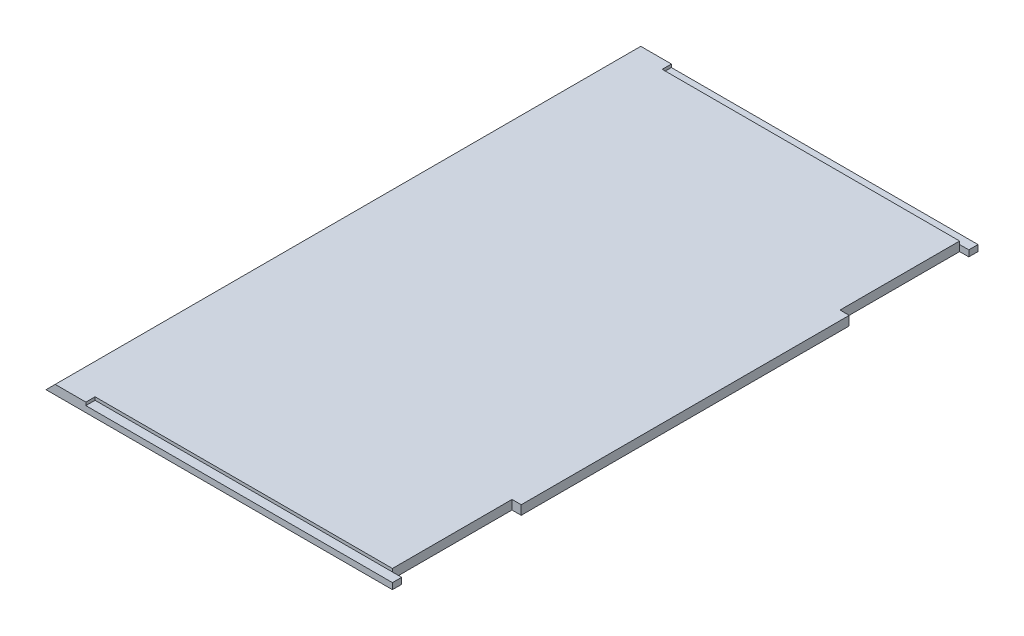
SolidWorks part; units mm, degrees
ref_plane "前视基准面" through (0, 0, 0) normal (0, 0, 1) x (1, 0, 0)
ref_plane "上视基准面" through (0, 0, 0) normal (0, 1, 0) x (1, 0, 0)
ref_plane "右视基准面" through (0, 0, 0) normal (1, 0, 0) x (0, 0, -1)
sketch "草图1" plane through (0, 0, 0) normal (0, 1, 0) x (1, 0, 0)
  line L1 (-44.5175, 10.5327) -> (75.4825, 10.5327)
  line L2 (-44.5175, 10.5327) -> (-44.5175, -180.4673)
  line L3 (-44.5175, -180.4673) -> (75.4825, -180.4673)
  line L4 (75.4825, 10.5327) -> (75.4825, -180.4673)
  dimension "D1" = 120
  dimension "D2" = 191
extrude "凸台-拉伸2" add sketch "草图1" along normal blind 3
chamfer "倒角7" distance 10 angle 45 1 edges at (-44.5175, 3, 84.9673)
sketch "草图2" plane through (0, 0, 0) normal (0, 1, 0) x (1, 0, 0)
  line L1 (-24.5175, -177.4673) -> (75.4825, -177.4673)
  line L2 (-24.5175, -177.4673) -> (-24.5175, -180.4673)
  line L3 (-24.5175, -180.4673) -> (75.4825, -180.4673)
  line L4 (75.4825, -177.4673) -> (75.4825, -180.4673)
  line L5 (-34.5175, -180.4673) -> (75.4825, -180.4673) construction
  line L6 (75.4825, -180.4673) -> (75.4825, 10.5327) construction
  line L7 (75.4825, 10.5327) -> (-34.5175, 10.5327) construction
  line L8 (-24.5175, 10.5327) -> (76.4476, 10.5327)
  line L9 (-24.5175, 10.5327) -> (-24.5175, 7.5327)
  line L10 (-24.5175, 7.5327) -> (75.4825, 7.5327)
  line L11 (75.4825, 10.5327) -> (75.4825, 7.5327)
  line L13 (72.4825, -177.4673) -> (72.4825, -138.4673)
  line L14 (72.4825, -138.4673) -> (75.4825, -138.4673)
  line L15 (75.4825, -177.4673) -> (75.4825, -138.4673)
  line L19 (72.4825, 10.5327) -> (72.4825, -31.4673)
  line L20 (72.4825, -31.4673) -> (76.4476, -31.4673)
  line L21 (76.4476, 10.5327) -> (76.4476, -31.4673)
  dimension "D1" = 100
  dimension "D2" = 3
  dimension "D3" = 3
  dimension "D4" = 100
  dimension "D5" = 100
  dimension "D6" = 3
  dimension "D7" = 3
  dimension "D8" = 42
  dimension "D9" = 3
sketch "草图3" plane through (0, 3, 0) normal (0, 1, 0) x (1, 0, 0)
  line L0 (75.4825, 10.5327) -> (-34.5175, 10.5327) construction
  line L1 (-24.5175, -177.4673) -> (75.4825, -177.4673)
  line L2 (-24.5175, -177.4673) -> (-24.5175, -180.4673)
  line L3 (-24.5175, -180.4673) -> (75.4825, -180.4673)
  line L4 (75.4825, -177.4673) -> (75.4825, -180.4673)
  line L5 (-24.5175, 10.5327) -> (75.4825, 10.5327)
  line L6 (-24.5175, 10.5327) -> (-24.5175, 7.5327)
  line L7 (-24.5175, 7.5327) -> (75.4825, 7.5327)
  line L8 (75.4825, 10.5327) -> (75.4825, 7.5327)
  line L9 (75.4825, -180.4673) -> (75.4825, 10.5327) construction
  dimension "D1" = 100
  dimension "D2" = 3
  dimension "D3" = 100
  dimension "D4" = 3
  dimension "D5" = 100
extrude "切除-拉伸4" cut sketch "草图3" against normal blind 1
sketch "草图6" plane through (0, 0, 0) normal (0, 1, 0) x (1, 0, 0)
  line L0 (75.4825, 10.5327) -> (-24.5175, 10.5327) construction
  line L1 (72.4825, 7.5327) -> (75.6777, 7.5327)
  line L2 (72.4825, 7.5327) -> (72.4825, -31.4673)
  line L3 (72.4825, -31.4673) -> (75.6777, -31.4673)
  line L4 (75.6777, 7.5327) -> (75.6777, -31.4673)
  line L5 (-24.5175, 7.5327) -> (75.4825, 7.5327) construction
  line L6 (75.4825, 10.5327) -> (75.4825, -180.4673) construction
  dimension "D1" = 42
  dimension "D2" = 0
  dimension "D3" = 3
extrude "切除-拉伸5" cut sketch "草图6" along normal through all
sketch "草图8" plane through (0, 0, 0) normal (0, 1, 0) x (1, 0, 0)
  line L1 (72.4825, -177.4673) -> (75.4825, -177.4673)
  line L2 (72.4825, -177.4673) -> (72.4825, -138.4673)
  line L3 (72.4825, -138.4673) -> (75.4825, -138.4673)
  line L4 (75.4825, -177.4673) -> (75.4825, -138.4673)
extrude "切除-拉伸6" cut sketch "草图8" along normal through all
